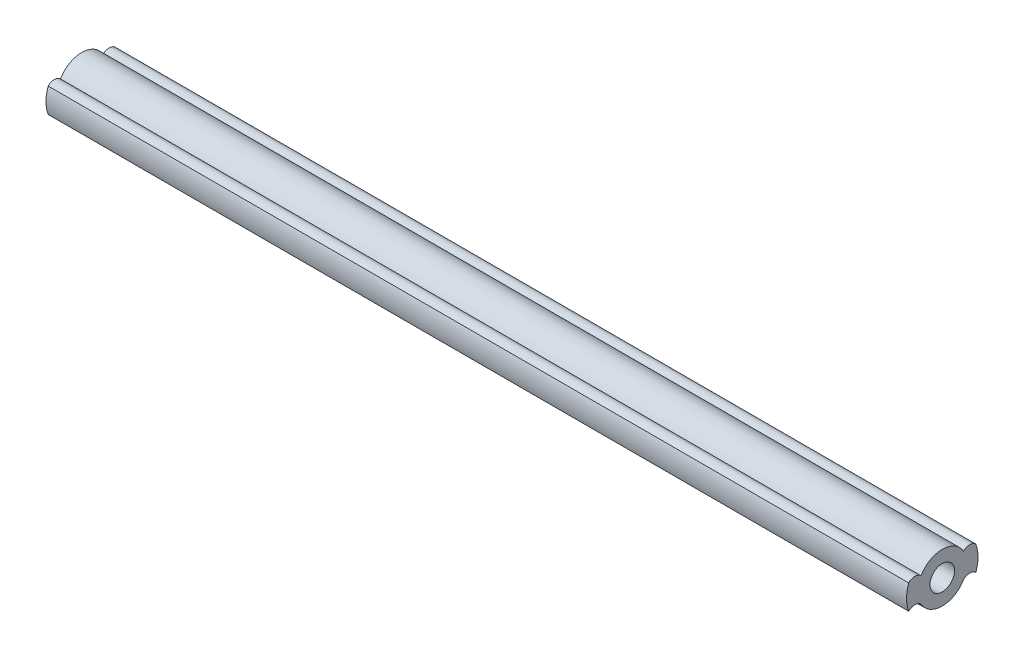
SolidWorks part; units mm, degrees
ref_plane "Front Plane" through (0, 0, 0) normal (0, 0, 1) x (1, 0, 0)
ref_plane "Top Plane" through (0, 0, 0) normal (0, 1, 0) x (1, 0, 0)
ref_plane "Right Plane" through (0, 0, 0) normal (1, 0, 0) x (0, 0, -1)
sketch "Sketch1" plane through (0, 0, 0) normal (1, 0, 0) x (0, 0, -1)
  circle A0 centre (0, 0) radius 10
  circle A1 centre (0, 0) radius 5
  arc A5 (8.6562, 5.007) -> (8.6538, -5.0112) centre (0, 0) cw
  arc A6 (8.6538, -5.0112) -> (13.6624, -5.0091) centre (11.1592, -7.5144) cw
  arc A7 (8.6562, 5.007) -> (13.6624, 5) centre (11.1559, 2.5004) cw
  arc A8 (13.6624, 5) -> (13.6624, -5.0091) centre (-0.2704, -0.0045) cw
  arc A9 (5, 8.6603) -> (5, -8.6603) centre (0, 0) cw
  arc A10 (-8.6562, 5.007) -> (-13.6624, 5) centre (-11.1559, 2.5004) ccw
  arc A11 (-8.6562, 5.007) -> (-8.6538, -5.0112) centre (0, 0) ccw
  arc A12 (-8.6538, -5.0112) -> (-13.6624, -5.0091) centre (-11.1592, -7.5144) ccw
  arc A13 (-13.6624, 5) -> (-13.6624, -5.0091) centre (0.2704, -0.0045) ccw
  circle A14 centre (4.9773, 0.2164) radius 0.018
extrude "Boss-Extrude1" add sketch "Sketch1" along normal blind 350 contours A0 A1 | A8 A7 A0 A6 | A10 A13 A12 A0 region at (0, -2.521, -9.3844) region at (0, 0.7601, -11.896) region at (0, 0.7601, 11.896)
